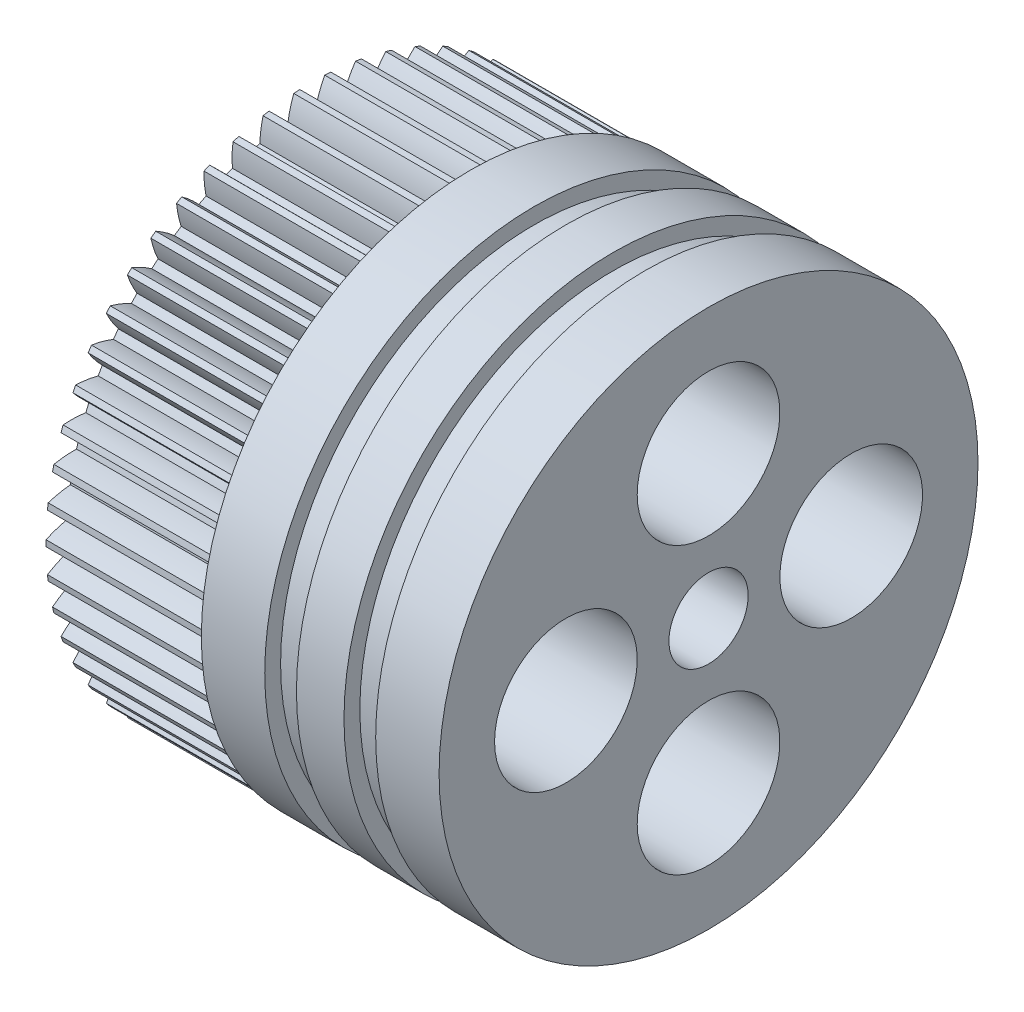
SolidWorks part; units mm, degrees
ref_plane "Plane1" through (0, 0, 0) normal (0, 0, 1) x (1, 0, 0)
ref_plane "Plane2" through (0, 0, 0) normal (0, 1, 0) x (1, 0, 0)
ref_plane "Plane3" through (0, 0, 0) normal (1, 0, 0) x (0, 0, -1)
other "Configuration Table"
sketch "HoldingSke" plane through (0, 0, 0) normal (0, 1, 0) x (1, 0, 0)
  line L0 (0, 0) -> (0.9796, -1.3484)
  line L1 (-15, 0) -> (100, 0) construction
  line L2 (0, 0) -> (-2.1039, 2.3779)
  line L3 (0, 0) -> (-11.863, 4.5341)
  line L4 (0, 0) -> (5.0761, 6.9867)
  line L5 (0, 0) -> (-46.8476, -17.4728)
  line L6 (0, 0) -> (-4.1448, -2.7965)
  line L7 (-2.1039, 2.3779) -> (8.6589, 51.2072)
  line L8 (-76.2, 54.61) -> (-75.7, 54.61)
  line L9 (-71.009, 38.7566) -> (-53.1078, 45.2721)
  line L10 (-76.2, 71.12) -> (104.1128, 71.12)
  line L11 (0, 0) -> (-5, 0)
  line L12 (-76.2, 101.6) -> (-76.177, 101.6)
  line L13 (24.9733, 27.94) -> (52.9518, 28.4284)
  line L14 (24.9733, 27.94) -> (24.9743, 27.94)
  line L15 (24.9733, 27.94) -> (100.4006, 29.5858)
  line L16 (-63.627, -0.6) -> (-12.827, -0.6)
  circle A0 centre (0, 0) radius 1.5
  circle A1 centre (0, 0) radius 15.449
  circle A2 centre (0, 0) radius 37.5
  circle A3 centre (0, 0) radius 1.5
  dimension "Num_teeth" = 54
  dimension "Pitch_radius" = 180.3128
  dimension "Width" = 5
sketch "BasProSke" plane through (0, 0, 0) normal (0, 1, 0) x (1, 0, 0)
  line L0 (-10, 0) -> (60, 0) construction
  line L1 (0, 0) -> (0, 16.8)
  line L2 (0, 0) -> (10, 0)
  line L3 (10, 0) -> (10, 16.8)
  line L4 (10, 16.8) -> (0, 16.8)
  dimension "Thickness" = 10
  dimension "Diameter" = 33.6
revolve "Base-Revolve" add sketch "BasProSke" angle 360 about L0
sketch "TooCutSke" plane through (0, 0, 0) normal (1, 0, 0) x (0, 0, -1)
  line L1 (0, 0) -> (0, 107) construction
  line L2 (0, 0) -> (-0.5114, 16.1919) construction
  line L3 (0, 0) -> (-1.8832, 32.3337) construction
  line L4 (-0.5114, 16.1919) -> (-0.9416, 16.1669) construction
  arc A0 (0.2608, 15.4468) -> (-0.2608, 15.4468) centre (0, 0) ccw
  arc A1 (0.7988, 16.8064) -> (-0.7988, 16.8064) centre (0, 0) ccw
  circle A2 centre (0, 0) radius 16.2 construction
  circle A3 centre (0, 0) radius 15.223 construction
  arc A4 (-0.2608, 15.4468) -> (-0.7988, 16.8064) centre (-6.5168, 13.7576) ccw
  arc A5 (0.7988, 16.8064) -> (0.2608, 15.4468) centre (6.5168, 13.7576) ccw
extrude "ToothCut" cut sketch "TooCutSke" along normal through all
fillet "Breaks" [suppressed] radius 0.012 tangent propagation no
fillet "RootFillets" [suppressed] radius 0.151
pattern_circular "TeethCuts" count 54 every 6.667 about axis through (-10, 0, 0) along (1, 0, 0) of "ToothCut", "RootFillets", "Breaks"
sketch "HubNeaOneSke" plane through (0, 0, 0) normal (-1, 0, 0) x (0, 0, 1)
  circle A0 centre (0, 0) radius 15.449
  dimension "Diameter" = 30.898
extrude "HubNearOne" [suppressed] add sketch "HubNeaOneSke" along normal blind 40.0014
sketch "HubNeaBotSke" plane through (0, 0, 0) normal (-1, 0, 0) x (0, 0, 1)
  circle A0 centre (0, 0) radius 15.449
  dimension "Diameter" = 30.898
extrude "HubNearBoth" [suppressed] add sketch "HubNeaBotSke" along normal blind 20.0007
ref_plane "FarPln" through (10, 0, 0) normal (1, 0, 0) x (0, 0, -1)
sketch "HubFarSke" plane through (10, 0, 0) normal (1, 0, 0) x (0, 0, -1)
  circle A0 centre (0, 0) radius 15.449
  dimension "Diameter" = 30.898
extrude "HubFar" [suppressed] add sketch "HubFarSke" along normal blind 20.0007
sketch "BorSke" plane through (0, 0, 0) normal (1, 0, 0) x (0, 0, -1)
  circle A0 centre (0, 0) radius 2
  dimension "Diameter" = 4
extrude "Bore" cut sketch "BorSke" along normal mid plane 100.0027
sketch "KeySke" plane through (0, 0, 0) normal (1, 0, 0) x (0, 0, -1)
  line L0 (-0.6, 0) -> (-0.6, 2)
  line L1 (-0.6, 2) -> (0.6, 2)
  line L2 (0.6, 2) -> (0.6, 0)
  line L3 (0, 0) -> (0, 34) construction
  line L4 (-0.6, 0) -> (0.6, 0)
  dimension "Width" = 1.2
extrude "Keyway" [suppressed] cut sketch "KeySke" along normal mid plane 100.0027
pattern_circular "Keyway2" [suppressed] count 2 every 90 about axis through (-10, 0, 0) along (1, 0, 0) reverse direction yes
sketch "Sketch1" plane through (10, 0, 0) normal (1, 0, 0) x (0, 0, -1)
  circle A0 centre (0, 0) radius 17
  circle A1 centre (0, 0) radius 2
  dimension "D1" = 34
  dimension "D2" = 4
extrude "Boss-Extrude1" add sketch "Sketch1" along normal blind 15
sketch "Sketch2" plane through (25, 0, 0) normal (1, 0, 0) x (0, 0, -1)
  circle A0 centre (0, 0) radius 2.5
  dimension "D1" = 5
extrude "Cut-Extrude1" cut sketch "Sketch2" against normal blind 5
sketch "Sketch3" plane through (0, 0, 0) normal (-1, 0, 0) x (0, 0, 1)
  circle A0 centre (0, 9) radius 4.5
  circle A1 centre (9, 0) radius 4.5
  circle A2 centre (0, -9) radius 4.5
  circle A3 centre (-9, 0) radius 4.5
  point P11 (0, 0)
  dimension "D1" = 4
  dimension "D3" = 9
  dimension "D2" = 9
extrude "Cut-Extrude2" cut sketch "Sketch3" against normal through all
ref_axis "Axis1" through (20, 0, 0) along (-1, 0, 0)
sketch "Sketch4" plane through (0, 0, 0) normal (0, 0, 1) x (1, 0, 0)
  line L0 (14, 17) -> (14, 16)
  line L1 (25, 17) -> (10, 17) construction
  line L2 (14, 16) -> (16, 16)
  line L3 (16, 16) -> (16, 17)
  line L4 (19, 17) -> (19, 16)
  line L5 (19, 16) -> (21, 16)
  line L6 (21, 16) -> (21, 17)
  line L7 (21, 17) -> (19, 17)
  line L8 (14, 17) -> (16, 17)
  line L9 (10, 17) -> (10, 19.1026) construction
  line L10 (10, 19.1026) -> (15, 19.1026) construction
  line L11 (15, 19.1026) -> (20, 19.1026) construction
  line L12 (20, 19.1026) -> (25, 19.1026) construction
  line L13 (25, 19.1026) -> (25, 17) construction
  point P16 (0, 0)
  point P19 (15, 17)
  point P20 (20, 17)
  dimension "D1" = 1
  dimension "D2" = 2
revolve "Cut-Revolve1" cut sketch "Sketch4" angle 360 about axis through (20, 0, 0) along (-1, 0, 0)
equation "' \"Module@HoldingSke\" = 6.35"
equation "' \"Num_teeth@HoldingSke\" = 12"
equation "' \"Ap@HoldingSke\" =  20"
equation "' \"Ap@HoldingSke\" = 20"
equation "'\"Width@HoldingSke\" = 0.5 * 25.4"
equation "' \"Hub_dia@HoldingSke\"= 1 * 25.4"
equation "' \"Hub_dia@HoldingSke\" = 1 * 25.4"
equation "' \"Overall_len@HoldingSke\" = 1.0 * 25.4"
equation "' \"Bore@HoldingSke\" = 0.75 * 25.4"
equation "' \"T_dim@HoldingSke\" = 0.1 * 25.4"
equation "' \"Width@KeySke\" = 0.25 * 25.4"
equation "' \"Show_teeth@HoldingSke\" = 13"
equation "' \"Backlash@HoldingSke\" = 0.009 * 25.4"
equation "' \"Addendum_fac@HoldingSke\" = 1.0"
equation "' \"Dedendum_fac@HoldingSke\" = 1.25"
equation "' \"Dedendum_add@HoldingSke\" = 0.00005 * 25.4"
equation "' \"Clearance_fac@HoldingSke\" = 0.25"
equation "\"Pitch@HoldingSke\" = 1 / \"Module@HoldingSke\""
equation "\"Overcut_dia@TooCutSke\" = (\"Num_teeth@HoldingSke\" + 2 * \"Addendum_fac@HoldingSke\") / \"Pitch@HoldingSke\" + 0.002 * 25.4"
equation "\"Pitch_dia@TooCutSke\" = \"Num_teeth@HoldingSke\" / \"Pitch@HoldingSke\""
equation "\"Base_dia@TooCutSke\" = \"Num_teeth@HoldingSke\" / \"Pitch@HoldingSke\" * cos((\"Ap@HoldingSke\"  * 3.14159265 / 180))"
equation "\"Root_dia@TooCutSke\" = (\"Num_teeth@HoldingSke\" + 2) / \"Pitch@HoldingSke\" - 2 * (\"Addendum_fac@HoldingSke\" + \"Dedendum_fac@HoldingSke\") / \"Pitch@HoldingSke\" - \"Dedendum_add@HoldingSke\" * 2"
equation "\"Half_ang@TooCutSke\" = 180 / \"Num_teeth@HoldingSke\""
equation "\"Half_CT@TooCutSke\" = \"Num_teeth@HoldingSke\" / \"Pitch@HoldingSke\" * sin((3.14159265 / 2 / \"Num_teeth@HoldingSke\")) / 2 - 7 * \"Backlash@HoldingSke\" / 4"
equation "\"Flank_rad@TooCutSke\" = \"Num_teeth@HoldingSke\" / \"Pitch@HoldingSke\" / 5"
equation "\"Radius@RootFillets\" = \"Clearance_fac@HoldingSke\" / \"Pitch@HoldingSke\" + \"Dedendum_add@HoldingSke\""
equation "\"Break_rad@Breaks\" = 0.02 / \"Pitch@HoldingSke\""
equation "\"Thickness@HoldingSke\"= \"Width@HoldingSke\""
equation "\"OAL@HoldingSke\" = \"Thickness@HoldingSke\""
equation "\"MHD@HoldingSke\" = (\"Num_teeth@HoldingSke\" + 2) / \"Pitch@HoldingSke\" - 2 * (\"Addendum_fac@HoldingSke\" + \"Dedendum_fac@HoldingSke\")  / \"Pitch@HoldingSke\" - \"Dedendum_add@HoldingSke\" * 2"
equation "\"MBD@HoldingSke\" = (\"Num_teeth@HoldingSke\" + 2) / \"Pitch@HoldingSke\" - 2 * (\"Addendum_fac@HoldingSke\" + \"Dedendum_fac@HoldingSke\")  / \"Pitch@HoldingSke\" - \"Dedendum_add@HoldingSke\" * 2 - 0.002 * 25.4"
equation "\"MHD@HoldingSke\" = ((sgn( \"MHD@HoldingSke\" - \"Hub_dia@HoldingSke\" )-1)*( \"MHD@HoldingSke\" - \"Hub_dia@HoldingSke\" ))/-2+ \"Hub_dia@HoldingSke\""
equation "\"MBD@HoldingSke\" = ((sgn( \"MBD@HoldingSke\" - \"Bore@HoldingSke\" )-1)*( \"MBD@HoldingSke\" - \"Bore@HoldingSke\" ))/-2+ \"Bore@HoldingSke\""
equation "\"OAL@HoldingSke\" = ((sgn( \"OAL@HoldingSke\" - \"Overall_len@HoldingSke\" )+1)*( \"OAL@HoldingSke\" - \"Overall_len@HoldingSke\" ))/2 + \"Overall_len@HoldingSke\" + 0.000002 * 25.4"
equation "\"Num_teeth@TeethCuts\" = int( \"Show_teeth@HoldingSke\" ) + 1"
equation "\"Num_teeth@TeethCuts\" = ((sgn( \"Num_teeth@TeethCuts\" - \"Num_teeth@HoldingSke\" )-1)*( \"Num_teeth@TeethCuts\" - \"Num_teeth@HoldingSke\" ))/-2+ \"Num_teeth@HoldingSke\""
equation "\"Num_teeth@TeethCuts\" = ((sgn( \"Num_teeth@TeethCuts\" - 2.0)+1)*( \"Num_teeth@TeethCuts\" - 2.0))/2 +2.0"
equation "\"Angle@TeethCuts\" = 360.0 / \"Num_teeth@HoldingSke\""
equation "\"Diameter@BasProSke\" = (\"Num_teeth@HoldingSke\" + 2 * \"Addendum_fac@HoldingSke\") / \"Pitch@HoldingSke\""
equation "' \"Fillet_rad@BasProSke\" =  \"Thickness@HoldingSke\" * 0.05"
equation "' \"Fillet_rad@BasProSke\" = \"Thickness@HoldingSke\" * 0.05"
equation "\"MHD@HoldingSke\" = ((sgn( \"MHD@HoldingSke\" - \"Root_dia@TooCutSke\" )-1)*( \"MHD@HoldingSke\" - \"Root_dia@TooCutSke\" ))/-2+ \"Root_dia@TooCutSke\""
equation "\"Diameter@HubNeaOneSke\" = \"MHD@HoldingSke\""
equation "\"Length@HubNearOne\" = \"OAL@HoldingSke\" - \"Thickness@BasProSke\""
equation "\"Diameter@HubNeaBotSke\" = \"MHD@HoldingSke\""
equation "\"Length@HubNearBoth\" = ( \"OAL@HoldingSke\" - \"Thickness@BasProSke\" ) / 2.0"
equation "\"Thickness@FarPln\" = \"Thickness@BasProSke\""
equation "\"Diameter@HubFarSke\" = \"MHD@HoldingSke\""
equation "\"Length@HubFar\" = ( \"OAL@HoldingSke\" - \"Thickness@BasProSke\" ) / 2.0"
equation "\"D1@Bore\" = \"OAL@HoldingSke\" * 2.0"
equation "\"D1@Keyway\" = \"OAL@HoldingSke\" * 2.0"
equation "\"Offset@KeySke\" = \"T_dim@HoldingSke\" + \"MBD@HoldingSke\" / 2.0"
